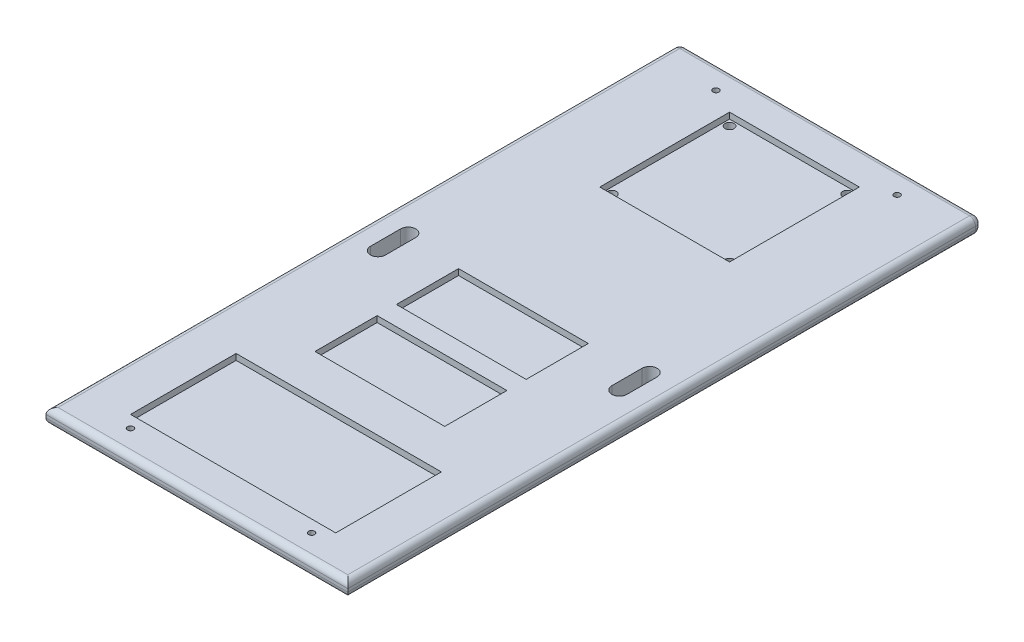
SolidWorks part; units mm, degrees
other "Marca1"
sketch "Croquis1" plane through (0, 2, -200) normal (0.4678, 0.1077, -0.8772) x (-0.8736, -0.0944, -0.4774)
ref_plane "Front Plane" through (0, 0, 0) normal (0, 0, 1) x (1, 0, 0)
ref_plane "Top Plane" through (0, 0, 0) normal (0, 1, 0) x (1, 0, 0)
ref_plane "Right Plane" through (0, 0, 0) normal (1, 0, 0) x (0, 0, -1)
sketch "Sketch3" plane through (0, 0, 0) normal (0, 1, 0) x (1, 0, 0)
  line L1 (-100, 0) -> (0, 0)
  line L2 (-100, 0) -> (-100, 210)
  line L3 (-100, 210) -> (0, 210)
  line L4 (0, 0) -> (0, 210)
  dimension "D1" = 210
  dimension "D2" = 100
extrude "Boss-Extrude2" add sketch "Sketch3" along normal blind 5
ref_plane "Plano1" through (0, 0, -105) normal (0, 0, -1) x (-1, 0, 0)
sketch "Sketch2" plane through (0, 0, 0) normal (0, -1, 0) x (-1, 0, 0)
  line L6 (3.5, 45.2) -> (8.5, 45.2) construction
  line L12 (8.5, 45.2) -> (8.5, 30.2) construction
  line L15 (8.5, 30.2) -> (3.5, 30.2) construction
  line L18 (8.4, 164.7) -> (3.6, 164.7)
  line L19 (8.4, 164.7) -> (8.4, 179.9)
  line L20 (8.4, 179.9) -> (3.6, 179.9)
  line L21 (3.6, 164.7) -> (3.6, 179.9)
  line L43 (3.5, 179.8) -> (8.5, 179.8) construction
  line L44 (8.5, 179.8) -> (8.5, 164.8) construction
  line L45 (8.5, 164.8) -> (3.5, 164.8) construction
  line L46 (3.5, 164.8) -> (3.5, 179.8) construction
  line L47 (3.5, 30.2) -> (3.5, 45.2) construction
  line L48 (91.5, 45.2) -> (91.5, 30.2) construction
  line L49 (91.5, 45.2) -> (91.5, 30.2) construction
  line L50 (91.5, 30.2) -> (96.5, 30.2) construction
  line L51 (96.5, 30.2) -> (96.5, 45.2) construction
  line L52 (96.5, 45.2) -> (91.5, 45.2) construction
  line L53 (96.5, 179.8) -> (91.5, 179.8) construction
  line L56 (91.5, 179.8) -> (91.5, 164.8) construction
  line L57 (91.5, 164.8) -> (96.5, 164.8) construction
  line L58 (96.5, 164.8) -> (96.5, 179.8) construction
  line L60 (91.4, 179.9) -> (96.6, 179.9)
  line L61 (91.4, 179.9) -> (91.4, 164.7)
  line L62 (91.4, 164.7) -> (96.6, 164.7)
  line L63 (96.6, 179.9) -> (96.6, 164.7)
  line L64 (96.4, 30.1) -> (91.6, 30.1)
  line L65 (96.4, 30.1) -> (96.4, 45.3)
  line L66 (96.4, 45.3) -> (91.6, 45.3)
  line L67 (91.6, 30.1) -> (91.6, 45.3)
  line L68 (8.4, 30.1) -> (3.6, 30.1)
  line L69 (8.4, 30.1) -> (8.4, 45.3)
  line L70 (8.4, 45.3) -> (3.6, 45.3)
  line L71 (3.6, 30.1) -> (3.6, 45.3)
  dimension "D5" = 0.1
  dimension "D1" = 0.1
  dimension "D2" = 0.1
  dimension "D3" = 0.1
  dimension "D4" = 0.1
  dimension "D6" = 0.1
  dimension "D7" = 0.1
  dimension "D8" = 0.1
  dimension "D9" = 0.1
  dimension "D10" = 0.1
  dimension "D11" = 0.1
  dimension "D12" = 0.1
  dimension "D13" = 0.1
  dimension "D14" = 0.1
  dimension "D15" = 0.1
  dimension "D16" = 0.1
extrude "Cortar-Extruir1" cut sketch "Sketch2" against normal blind 2
fillet "Fillet1" radius 2 10 edges at (-50, 5, -210) (-100, 5, -105) (0, 5, -105) (-50, 5, 0) (0, 2.5, -210) (-100, 2.5, -210) (-50, 0, -210) (-100, 0, -105) (-50, 0, 0) (0, 0, -105)
sketch "Sketch4" plane through (0, 5, 0) normal (0, 1, 0) x (1, 0, 0)
  line L0 (-100, 105) -> (-2, 105) construction
  line L1 (-100, 200) -> (0, 200)
  line L2 (-100, 200) -> (-100, 10)
  line L3 (-100, 10) -> (0, 10)
  line L4 (0, 200) -> (0, 10)
  line L5 (0, 10) -> (-100, 10)
  line L6 (0, 10) -> (0, 200)
  line L7 (0, 200) -> (-100, 200)
  line L8 (-100, 10) -> (-100, 200)
  line L9 (-2, 2) -> (-2, 208) construction
  line L10 (-50, 200) -> (-50, 2) construction
  line L11 (-98, 2) -> (-2, 2) construction
  line L12 (-10, 110) -> (-10, 100) construction
  line L13 (-7.5, 110) -> (-7.5, 100)
  line L14 (-12.5, 110) -> (-12.5, 100)
  line L15 (-90, 110) -> (-90, 100) construction
  line L16 (-92.5, 110) -> (-92.5, 100)
  line L17 (-87.5, 110) -> (-87.5, 100)
  arc A0 (-7.5, 110) -> (-12.5, 110) centre (-10, 110) ccw
  arc A1 (-12.5, 100) -> (-7.5, 100) centre (-10, 100) ccw
  arc A2 (-92.5, 110) -> (-87.5, 110) centre (-90, 110) cw
  arc A3 (-87.5, 100) -> (-92.5, 100) centre (-90, 100) cw
  point P16 (-10, 105)
  point P25 (-90, 105)
  dimension "D1" = 10
  dimension "D2" = 5
  dimension "D3" = 8
extrude "Cut-Extrude1" cut sketch "Sketch4" against normal through all both and the other way through all contours L16 A3 L17 A2 | L14 A1 L13 A0
sketch "Sketch6" plane through (0, 5, 0) normal (0, 1, 0) x (1, 0, 0)
  line L0 (-50, 2) -> (-50, 208) construction
  line L1 (-98, 2) -> (-2, 2) construction
  line L2 (-2, 208) -> (-98, 208) construction
  line L3 (-98, 105) -> (-2, 105) construction
  line L4 (-98, 208) -> (-98, 2) construction
  line L5 (-2, 2) -> (-2, 208) construction
  line L6 (-71.5, 176.5) -> (-28.5, 176.5) construction
  line L7 (-98, 208) -> (-2, 208)
  line L8 (-98, 208) -> (-98, 2) construction
  line L9 (-98, 2) -> (-2, 2)
  line L10 (-2, 208) -> (-2, 2)
  line L11 (-16, 47) -> (-84, 47)
  line L12 (-16, 47) -> (-16, 12)
  line L13 (-16, 12) -> (-84, 12)
  line L14 (-84, 47) -> (-84, 12)
  line L15 (-16, 47) -> (-84, 12) construction
  line L16 (-16, 12) -> (-84, 47) construction
  line L17 (-28.5, 198) -> (-71.5, 198)
  line L18 (-28.5, 198) -> (-28.5, 155)
  line L19 (-28.5, 155) -> (-71.5, 155)
  line L20 (-71.5, 198) -> (-71.5, 155)
  line L21 (-28.5, 198) -> (-71.5, 155) construction
  line L22 (-28.5, 155) -> (-71.5, 198) construction
  line L29 (-50, 198) -> (-50, 155) construction
  line L30 (-600.1542, 245.4641) -> (-643.1542, 245.4641)
  line L31 (-600.1542, 245.4641) -> (-600.1542, 224.8641)
  line L32 (-600.1542, 224.8641) -> (-643.1542, 224.8641)
  line L33 (-643.1542, 245.4641) -> (-643.1542, 224.8641)
  line L34 (-600.9449, 222.2918) -> (-643.9449, 222.2918)
  line L35 (-600.9449, 222.2918) -> (-600.9449, 201.6918)
  line L36 (-600.9449, 201.6918) -> (-643.9449, 201.6918)
  line L37 (-643.9449, 222.2918) -> (-643.9449, 201.6918)
  line L43 (-71.5, 60.6227) -> (-28.5, 60.6227)
  line L44 (-71.5, 60.6227) -> (-71.5, 81.2227)
  line L45 (-71.5, 81.2227) -> (-28.5, 81.2227)
  line L46 (-28.5, 60.6227) -> (-28.5, 81.2227)
  line L47 (-71.5, 60.6227) -> (-28.5, 81.2227) construction
  line L48 (-71.5, 81.2227) -> (-28.5, 60.6227) construction
  line L49 (-71.5, 108.2043) -> (-28.5, 108.2043)
  line L50 (-71.5, 108.2043) -> (-71.5, 87.6043)
  line L51 (-71.5, 87.6043) -> (-28.5, 87.6043)
  line L52 (-28.5, 108.2043) -> (-28.5, 87.6043)
  circle A0 centre (-80, 202) radius 1
  circle A1 centre (-20, 202) radius 1
  circle A2 centre (-20, 8) radius 1
  circle A3 centre (-80, 8) radius 1
  circle A4 centre (-30.5, 196) radius 1.5
  circle A5 centre (-30.5, 157) radius 1.5
  circle A6 centre (-69.5, 157) radius 1.5
  circle A7 centre (-69.5, 196) radius 1.5
  point P26 (-50, 29.5)
  point P31 (-50, 176.5)
  point P36 (-50, 155)
  point P37 (-50, 139.7)
  point P62 (-50, 70.9227)
  point P67 (-50, 139.7)
  dimension "D1" = 18
  dimension "D3" = 2
  dimension "D13" = 3
  dimension "D2" = 6
  dimension "D4" = 68
  dimension "D5" = 35
  dimension "D6" = 10
  dimension "D7" = 43
  dimension "D8" = 43
  dimension "D9" = 10
  dimension "D10" = 43
  dimension "D11" = 20.6
  dimension "D14" = 2
  dimension "D15" = 2
  dimension "D16" = 20.6
  dimension "D17" = 43
extrude "Cut-Extrude2" cut sketch "Sketch6" against normal blind 3 contours A3 | A2 | A1 | A0
extrude "AgujerosL298N" cut sketch "Sketch6<4>" against normal through all contours A4 | A6 | A5 | A7 region at (-30.5, 5, -196) region at (-30.5, 5, -157) region at (-69.5, 5, -157)
sketch "Sketch6<4>" plane through (0, 5, 0) normal (0, 1, 0) x (1, 0, 0) same geometry as "Sketch6"
extrude "Cortar-Extruir2" cut sketch "Sketch6<6>" against normal blind 2 contours L50 | L43 L46 L45 L44 | L17 L20 L19 L18 A5 A4 A6 A7 | L11 L14 L13 L12 region at (-50, 5, -29.5) region at (-50, 5, -176.5) region at (-50, 5, -70.9227) region at (-50, 5, -97.9043)
sketch "Sketch6<6>" plane through (0, 5, 0) normal (0, 1, 0) x (1, 0, 0) same geometry as "Sketch6"
